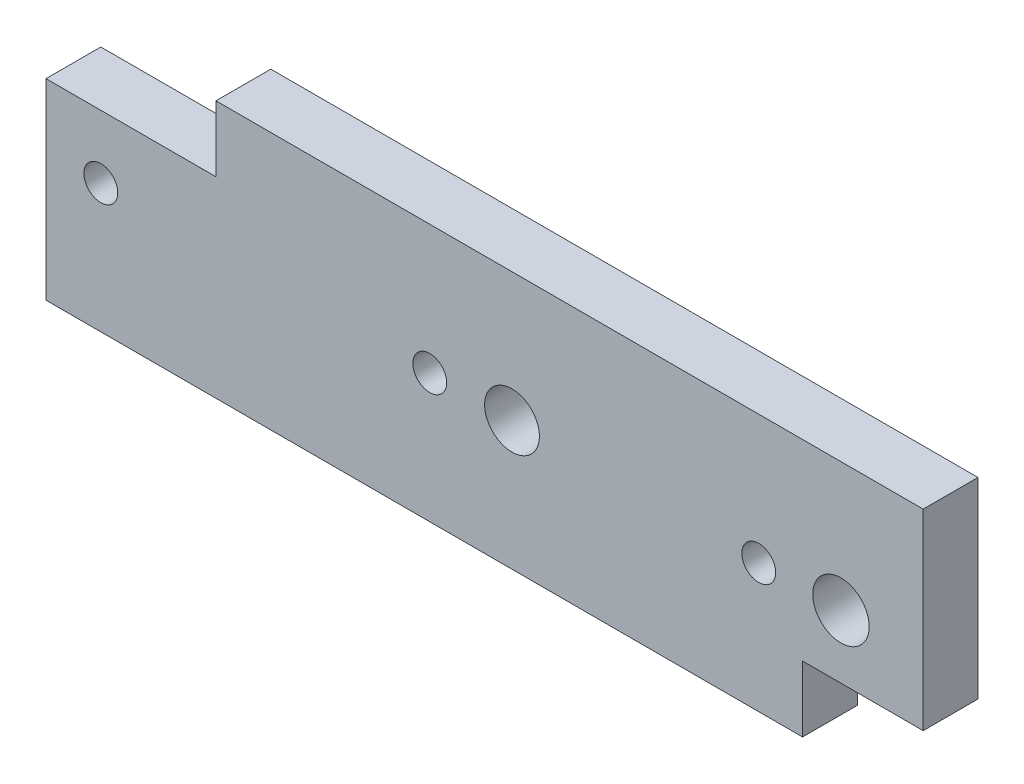
SolidWorks part; units mm, degrees
ref_plane "Front Plane" through (0, 0, 0) normal (0, 0, 1) x (1, 0, 0)
ref_plane "Top Plane" through (0, 0, 0) normal (0, 1, 0) x (1, 0, 0)
ref_plane "Right Plane" through (0, 0, 0) normal (1, 0, 0) x (0, 0, -1)
sketch "Sketch1" plane through (0, 0, 0) normal (0, 0, 1) x (1, 0, 0)
  line L1 (-130, -23.5) -> (30, -23.5)
  line L2 (-130, -23.5) -> (-130, 23.5)
  line L3 (-130, 23.5) -> (30, 23.5)
  line L4 (30, -23.5) -> (30, 23.5)
extrude "Boss-Extrude1" add sketch "Sketch1" along normal blind 10
sketch "Sketch3" plane through (0, 0, 0) normal (0, 0, -1) x (-1, 0, 0)
  line L0 (-30, -11.5) -> (130, -11.5) construction
  line L1 (-30, -11.5) -> (-8, -11.5)
  line L2 (-8, -23.5) -> (-8, -26.65) construction
  line L3 (-8, -11.5) -> (-8, -23.5)
  line L4 (-30, 11.5) -> (130, 11.5) construction
  line L5 (99, 11.5) -> (130, 11.5)
  line L6 (139, 23.5) -> (139, 26.65) construction
  line L7 (139, 23.5) -> (139, 26.65)
  line L8 (99, 11.5) -> (99, 23.5)
  line L9 (99, 23.5) -> (99, 26.65) construction
  line L10 (-30, -23.5) -> (-30, 23.5) construction
  line L11 (130, -23.5) -> (-30, -23.5) construction
  line L12 (-30, -23.5) -> (-30, -11.5)
  line L13 (-8, -23.5) -> (-30, -23.5)
  line L14 (-30, 23.5) -> (130, 23.5) construction
  line L15 (130, 23.5) -> (130, -23.5) construction
  line L16 (99, 23.5) -> (130, 23.5)
  line L17 (130, 23.5) -> (130, 11.5)
  line M8 (130, -23.5) -> (130, 23.5)
  line M9 (130, 23.5) -> (-30, 23.5)
  line M10 (-30, 23.5) -> (-30, -23.5)
  line M11 (-30, -23.5) -> (130, -23.5)
  dimension "D1" = 40
extrude "Cut-Extrude1" cut sketch "Sketch3" against normal blind 10 contours L8 L5 M8 M9 | L3 L1 M10 M11 region at (19, -17.5, 0) region at (-114.5, 17.5, 0)
sketch "Sketch4" plane through (0, 0, 10) normal (0, 0, 1) x (1, 0, 0)
  circle A0 centre (-45, 0) radius 5 construction
  circle A1 centre (15, 0) radius 5.1464 construction
  circle A2 centre (0, 0) radius 3.0879 construction
  arc A3 (-17.5, 17.5) -> (-23.5, 17.5) centre (-20.5, 17.5) ccw construction
  circle A4 centre (-60, 0) radius 3.0879 construction
  circle A5 centre (-120, 0) radius 3.0879 construction
  circle A6 centre (-45, 0) radius 5
  circle A7 centre (15, 0) radius 5.1464
  circle A8 centre (0, 0) radius 3.0879
  arc A9 (-17.5, 17.5) -> (-23.5, 17.5) centre (-20.5, 17.5) ccw
  circle A10 centre (-60, 0) radius 3.0879
  circle A11 centre (-120, 0) radius 3.0879
extrude "Cut-Extrude2" cut sketch "Sketch4" against normal blind 10 contours A7 | A8 | A6 | A10 | A11 region at (-45, 0, 10) region at (15, 0, 10) region at (0, 0, 10) region at (-60, 0, 10) region at (-120, 0, 10)
